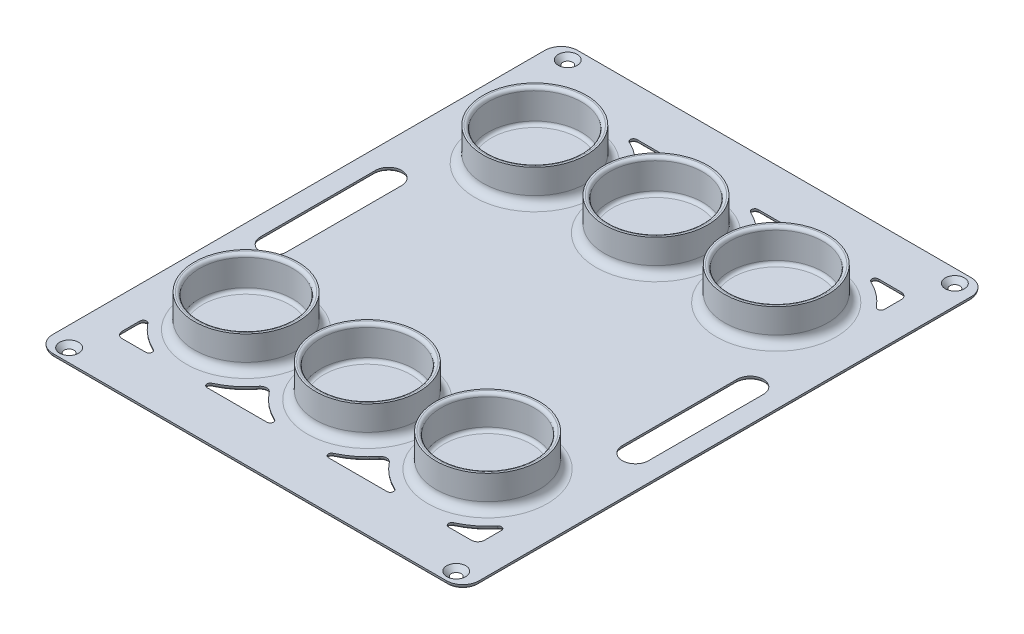
SolidWorks part; units mm, degrees
material "3.0205 (EN-AW 1200)"
ref_plane "Front Plane" through (0, 0, 0) normal (0, 0, 1) x (1, 0, 0)
ref_plane "Top Plane" through (0, 0, 0) normal (0, 1, 0) x (1, 0, 0)
ref_plane "Right Plane" through (0, 0, 0) normal (1, 0, 0) x (0, 0, -1)
sketch "Sketch3" plane through (0, 0, 0) normal (0, 1, 0) x (1, 0, 0)
  line L1 (-60, 80) -> (60, 80)
  line L2 (-65, 75) -> (-65, -75)
  line L3 (-60, -80) -> (60, -80)
  line L4 (65, 75) -> (65, -75)
  line L5 (-65, 80) -> (65, -80) construction
  line L6 (-65, -80) -> (65, 80) construction
  arc A0 (-65, -75) -> (-60, -80) centre (-60, -75) ccw
  arc A1 (60, -80) -> (65, -75) centre (60, -75) ccw
  arc A2 (60, 80) -> (65, 75) centre (60, 75) cw
  arc A3 (-60, 80) -> (-65, 75) centre (-60, 75) ccw
  point P0 (0, 0)
  dimension "D3" = 5
  dimension "D1" = 160
  dimension "D2" = 130
extrude "Boss-Extrude1" add sketch "Sketch3" along normal blind 1.5
sketch "Sketch5" plane through (0, 1.5, 0) normal (0, 1, 0) x (1, 0, 0)
  circle A0 centre (0.1497, 43.7424) radius 14.25
  circle A1 centre (0.1497, -44.2576) radius 14.25
  circle A2 centre (36.8039, -44.2576) radius 14.25
  circle A3 centre (36.8039, 43.7424) radius 14.25
  circle A4 centre (-36.8039, -44.2576) radius 14.25
  circle A5 centre (-36.8039, 43.7424) radius 14.25
  circle A6 centre (0.1497, 43.7424) radius 15.75
  circle A7 centre (0.1497, -44.2576) radius 15.75
  circle A8 centre (36.8039, -44.2576) radius 15.75
  circle A9 centre (36.8039, 43.7424) radius 15.75
  circle A10 centre (-36.8039, -44.2576) radius 15.75
  circle A11 centre (-36.8039, 43.7424) radius 15.75
  dimension "D1" = 28.5
  dimension "D3" = 36.8039
  dimension "D4" = 36.8039
  dimension "D6" = 43.7424
  dimension "D7" = 43.7424
  dimension "D9" = 43.7424
  dimension "D10" = 36.8039
  dimension "D11" = 44.2576
  dimension "D12" = 44.2576
  dimension "D13" = 28.5
  dimension "D14" = 28.5
  dimension "D15" = 28.5
  dimension "D16" = 28.5
  dimension "D17" = 28.5
  dimension "D5" = 44.2576
  dimension "D8" = 36.8039
  dimension "D2" = 1.5
extrude "Boss-Extrude2" add sketch "Sketch5" along normal blind 10
fillet "Fillet2" radius 1 6 edges at (36.8039, 11.5, 30.0076) (36.8039, 1.5, -29.4924) (0.1497, 11.5, -29.4924) (0.1497, 1.5, 58.5076) (-36.8039, 1.5, 58.5076) (-36.8039, 11.5, -29.4924)
fillet "Fillet3" radius 1 6 edges at (-36.8039, 11.5, 30.0076) (0.1497, 11.5, 30.0076) (36.8039, 1.5, 58.5076) (36.8039, 11.5, -29.4924) (0.1497, 1.5, -29.4924) (-36.8039, 1.5, -29.4924)
sketch "Sketch6" plane through (0, 1.5, 0) normal (0, 1, 0) x (1, 0, 0)
  line L0 (-65, 75) -> (-65, -75) construction
  line L1 (60, 80) -> (-60, 80) construction
  line L3 (-60, -80) -> (60, -80) construction
  point P0 (59, -76)
  point P1 (59, 76)
  point P2 (-59, 76)
  point P3 (-59, -76)
  dimension "D1" = 118
  dimension "D2" = 152
  dimension "D3" = 6
  dimension "D4" = 4
  dimension "D5" = 4
  dimension "D6" = 4
  dimension "D7" = 152
  dimension "D8" = 4
hole_wizard "CSK for M2.5 Flat Head Machine Screw1" positions "Sketch8" profile "Sketch9" countersink size "M2.5" standard "ANSI Metric" end condition through all
sketch "Sketch8" plane through (0, 1.5, 0) normal (0, 1, 0) x (1, 0, 0)
  point P0 (-59, 76)
  point P3 (59, 76)
  point P6 (59, -76)
  point P9 (-59, -76)
sketch "Sketch9" plane through (-59, 1.5, -76) normal (1, 0, 0) x (0, 0, 1)
  line L0 (0, 0) -> (0, 1.5)
  line L1 (0, 1.5) -> (1.5, 1.5)
  line L2 (1.5, 1.5) -> (1.5, 1.4)
  line L3 (1.5, 1.4) -> (2.9, 0)
  line L5 (2.9, 0) -> (0, 0)
  line L6 (-1.5, 1.4) -> (-2.9, 0) construction
  line L11 (0, -6.35) -> (0, 107.95) construction
  dimension "Thru Hole Dia." = 3
  dimension "Thru Hole Depth" = 1.5
  dimension "Near C'Sink Dia." = 5.8
  dimension "Near C'Sink Angle" = 90
sketch "Sketch11" plane through (0, 1.5, 0) normal (0, 1, 0) x (1, 0, 0)
  line L0 (-36.8039, -44.2576) -> (0.1497, -44.2576) construction
  line L1 (0.1497, -44.2576) -> (36.8039, -44.2576) construction
  line L2 (-18.3271, -44.2576) -> (-18.3271, -65.5202) construction
  line L3 (18.4768, -44.2576) -> (18.4768, -65.5202) construction
  line L4 (-27.4509, -65.5202) -> (-9.2033, -65.5202)
  line L5 (9.5295, -65.5202) -> (27.4241, -65.5202)
  line L6 (36.8039, -44.2576) -> (36.8039, -65.2117) construction
  line L7 (-36.8039, -44.2576) -> (-36.8039, -64.8023) construction
  line L10 (-55.2807, -58.1361) -> (-55.2807, -63.5202)
  line L11 (-53.2807, -65.5202) -> (-46.1569, -65.5202)
  line L12 (55.131, -58.3403) -> (55.131, -63.5202)
  line L13 (53.131, -65.5202) -> (46.1837, -65.5202)
  line L18 (0, 0) -> (63.2199, 0) construction
  line L19 (-36.8039, 44.2576) -> (-36.8039, 64.8023) construction
  line L20 (36.8039, 44.2576) -> (36.8039, 65.2117) construction
  line L21 (18.4768, 44.2576) -> (18.4768, 65.5202) construction
  line L22 (-18.3271, 44.2576) -> (-18.3271, 65.5202) construction
  line L23 (0.1497, 44.2576) -> (36.8039, 44.2576) construction
  line L24 (-36.8039, 44.2576) -> (0.1497, 44.2576) construction
  line L29 (53.131, 65.5202) -> (46.1837, 65.5202)
  line L30 (55.131, 58.3403) -> (55.131, 63.5202)
  line L31 (-53.2807, 65.5202) -> (-46.1569, 65.5202)
  line L32 (-55.2807, 58.1361) -> (-55.2807, 63.5202)
  line L35 (9.5295, 65.5202) -> (27.4241, 65.5202)
  line L36 (-27.4509, 65.5202) -> (-9.2033, 65.5202)
  line L37 (55.131, 17.5) -> (55.131, -17.5) construction
  line L40 (59.131, 17.5) -> (59.131, -17.5)
  line L41 (51.131, 17.5) -> (51.131, -17.5)
  line L42 (0, 0) -> (0, -21.7928) construction
  line L43 (-55.131, 17.5) -> (-55.131, -17.5) construction
  line L44 (-59.131, 17.5) -> (-59.131, -17.5)
  line L45 (-51.131, 17.5) -> (-51.131, -17.5)
  arc A0 (-27.87, -63.6122) -> (-19.9119, -57.2606) centre (-36.8039, -44.2576) ccw
  arc A1 (-16.7423, -57.2606) -> (-8.7842, -63.6122) centre (0.1497, -44.2576) ccw
  arc A2 (9.1094, -63.6127) -> (16.9056, -57.4537) centre (0.1497, -44.2576) ccw
  arc A3 (20.048, -57.4537) -> (27.8442, -63.6127) centre (36.8039, -44.2576) ccw
  circle A4 centre (-36.8039, -44.2576) radius 15.75 construction
  circle A5 centre (0.1497, -44.2576) radius 15.75 construction
  circle A6 centre (36.8039, -44.2576) radius 15.75 construction
  arc A7 (-45.7378, -63.6122) -> (-53.4976, -57.5142) centre (-36.8039, -44.2576) cw
  arc A8 (53.355, -57.7096) -> (45.7636, -63.6127) centre (36.8039, -44.2576) cw
  arc A9 (16.9056, -57.4537) -> (20.048, -57.4537) centre (18.4768, -58.6911) cw
  arc A10 (-19.9119, -57.2606) -> (-16.7423, -57.2606) centre (-18.3271, -58.4806) cw
  arc A11 (53.355, -57.7096) -> (55.131, -58.3403) centre (54.131, -58.3403) cw
  arc A12 (45.7636, -63.6127) -> (46.1837, -65.5202) centre (46.1837, -64.5202) ccw
  arc A13 (27.4241, -65.5202) -> (27.8442, -63.6127) centre (27.4241, -64.5202) ccw
  arc A14 (9.5295, -65.5202) -> (9.1094, -63.6127) centre (9.5295, -64.5202) cw
  arc A15 (-9.2033, -65.5202) -> (-8.7842, -63.6122) centre (-9.2033, -64.5202) ccw
  arc A16 (-27.4509, -65.5202) -> (-27.87, -63.6122) centre (-27.4509, -64.5202) cw
  arc A17 (-45.7378, -63.6122) -> (-46.1569, -65.5202) centre (-46.1569, -64.5202) cw
  arc A18 (-53.4976, -57.5142) -> (-55.2807, -58.1361) centre (-54.2807, -58.1361) ccw
  arc A19 (55.131, -63.5202) -> (53.131, -65.5202) centre (53.131, -63.5202) cw
  arc A20 (-55.2807, -63.5202) -> (-53.2807, -65.5202) centre (-53.2807, -63.5202) ccw
  arc A57 (-55.2807, 63.5202) -> (-53.2807, 65.5202) centre (-53.2807, 63.5202) cw
  arc A58 (55.131, 63.5202) -> (53.131, 65.5202) centre (53.131, 63.5202) ccw
  arc A59 (-53.4976, 57.5142) -> (-55.2807, 58.1361) centre (-54.2807, 58.1361) cw
  arc A60 (-45.7378, 63.6122) -> (-46.1569, 65.5202) centre (-46.1569, 64.5202) ccw
  arc A61 (-27.4509, 65.5202) -> (-27.87, 63.6122) centre (-27.4509, 64.5202) ccw
  arc A62 (-9.2033, 65.5202) -> (-8.7842, 63.6122) centre (-9.2033, 64.5202) cw
  arc A63 (9.5295, 65.5202) -> (9.1094, 63.6127) centre (9.5295, 64.5202) ccw
  arc A64 (27.4241, 65.5202) -> (27.8442, 63.6127) centre (27.4241, 64.5202) cw
  arc A65 (45.7636, 63.6127) -> (46.1837, 65.5202) centre (46.1837, 64.5202) cw
  arc A66 (53.355, 57.7096) -> (55.131, 58.3403) centre (54.131, 58.3403) ccw
  arc A67 (-19.9119, 57.2606) -> (-16.7423, 57.2606) centre (-18.3271, 58.4806) ccw
  arc A68 (16.9056, 57.4537) -> (20.048, 57.4537) centre (18.4768, 58.6911) ccw
  arc A69 (53.355, 57.7096) -> (45.7636, 63.6127) centre (36.8039, 44.2576) ccw
  arc A70 (-45.7378, 63.6122) -> (-53.4976, 57.5142) centre (-36.8039, 44.2576) ccw
  arc A71 (20.048, 57.4537) -> (27.8442, 63.6127) centre (36.8039, 44.2576) cw
  arc A72 (9.1094, 63.6127) -> (16.9056, 57.4537) centre (0.1497, 44.2576) cw
  arc A73 (-16.7423, 57.2606) -> (-8.7842, 63.6122) centre (0.1497, 44.2576) cw
  arc A74 (-27.87, 63.6122) -> (-19.9119, 57.2606) centre (-36.8039, 44.2576) cw
  arc A77 (59.131, 17.5) -> (51.131, 17.5) centre (55.131, 17.5) ccw
  arc A78 (51.131, -17.5) -> (59.131, -17.5) centre (55.131, -17.5) ccw
  arc A79 (-59.131, 17.5) -> (-51.131, 17.5) centre (-55.131, 17.5) cw
  arc A80 (-51.131, -17.5) -> (-59.131, -17.5) centre (-55.131, -17.5) cw
  point P13 (-18.3271, -65.5202)
  point P16 (18.4768, -65.5202)
  point P38 (18.4768, -55.1669)
  point P41 (-18.3271, -54.8889)
  point P44 (55.131, -55.1669)
  point P47 (35.131, -65.5202)
  point P50 (38.4768, -65.5202)
  point P53 (-1.5232, -65.5202)
  point P56 (1.6729, -65.5202)
  point P59 (-38.3271, -65.5202)
  point P62 (-35.2807, -65.5202)
  point P65 (-55.2807, -54.8889)
  point P72 (55.131, 0)
  point P80 (-55.131, 0)
  point P214 (-55.2807, 54.8889)
  point P215 (-35.2807, 65.5202)
  point P216 (-38.3271, 65.5202)
  point P217 (1.6729, 65.5202)
  point P218 (-1.5232, 65.5202)
  point P219 (38.4768, 65.5202)
  point P220 (35.131, 65.5202)
  point P221 (55.131, 55.1669)
  point P222 (-18.3271, 54.8889)
  point P223 (18.4768, 55.1669)
  point P224 (18.4768, 65.5202)
  point P225 (-18.3271, 65.5202)
  dimension "D1" = 2
  dimension "D4" = 1
  dimension "D5" = 2
  dimension "D2" = 40
  dimension "D3" = 40
  dimension "D6" = 35
  dimension "D7" = 8
extrude "Cut-Extrude2" cut sketch "Sketch11" against normal through all
fillet "Fillet4" radius 2.5 6 edges at (-36.8039, 1.5, -27.9924) (0.1497, 1.5, -27.9924) (36.8039, 1.5, -27.9924) (36.8039, 1.5, 28.5076) (0.1497, 1.5, 28.5076) (-36.8039, 1.5, 28.5076)
fillet "Fillet5" radius 1.5 68 edges at (-54.6949, 0, 64.9344) (-55.2807, 0, 60.8281) (-54.61, 0, 57.1919) (-49.9755, 0, 61.0185) (-45.1802, 0, 64.7347) (-49.7188, 0, 65.5202) (54.5452, 0, 64.9344) (49.6573, 0, 65.5202) (45.2071, 0, 64.7352) (49.8963, 0, 61.0946) (54.4656, 0, 57.398) (55.131, 0, 60.9302) (-8.2266, 0, 64.7347) (-18.3271, 0, 65.5202) (-28.4276, 0, 64.7347) (-23.5061, 0, 60.9185) (-18.3271, 0, 56.4806) (-13.148, 0, 60.9185) (54.4656, 0, -57.398) (49.8963, 0, -61.0946) (45.2071, 0, -64.7352) (49.6573, 0, -65.5202) (54.5452, 0, -64.9344) (55.131, 0, -60.9302) (-8.2266, 0, -64.7347) (-13.148, 0, -60.9185) (-18.3271, 0, -56.4806) (-23.5061, 0, -60.9185) (-28.4276, 0, -64.7347) (-18.3271, 0, -65.5202) (28.4007, 0, -64.7352) (23.5825, 0, -60.9935) (18.4768, 0, -56.6911) (13.3711, 0, -60.9935) (8.5529, 0, -64.7352) (18.4768, 0, -65.5202) (-45.1802, 0, -64.7347) (-49.9755, 0, -61.0185) (-54.61, 0, -57.1919) (-55.2807, 0, -60.8281) (-54.6949, 0, -64.9344) (-49.7188, 0, -65.5202) (28.4007, 0, 64.7352) (18.4768, 0, 65.5202) (8.5529, 0, 64.7352) (13.3711, 0, 60.9935) (18.4768, 0, 56.6911) (23.5825, 0, 60.9935) (0, 0, 80) (63.5355, 0, 78.5355) (65, 0, 0) (63.5355, 0, -78.5355) (0, 0, -80) (-63.5355, 0, -78.5355) (-65, 0, 0) (-63.5355, 0, 78.5355) (-59, 0, 77.5) (59, 0, 77.5) (59, 0, -74.5) (-59, 0, -74.5) (-55.131, 0, 21.5) (-59.131, 0, 0) (-55.131, 0, -21.5) (-51.131, 0, 0) (55.131, 0, 21.5) (51.131, 0, 0) (55.131, 0, -21.5) (59.131, 0, 0)
